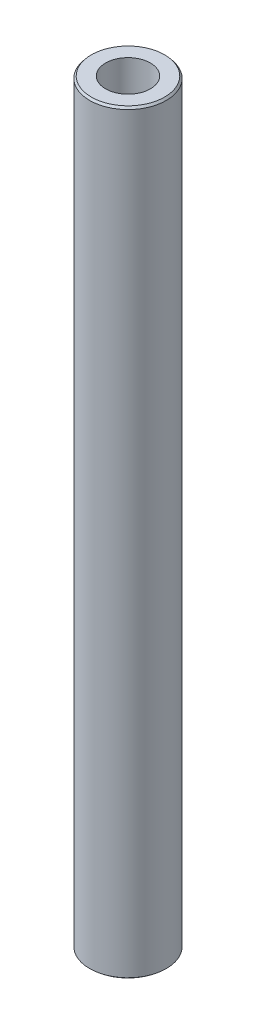
SolidWorks part; units mm, degrees
ref_plane "Front Plane" through (0, 0, 0) normal (0, 0, 1) x (1, 0, 0)
ref_plane "Top Plane" through (0, 0, 0) normal (0, 1, 0) x (1, 0, 0)
ref_plane "Right Plane" through (0, 0, 0) normal (1, 0, 0) x (0, 0, -1)
sketch "Sketch1" plane through (0, 0, 0) normal (0, 1, 0) x (1, 0, 0)
  circle A0 centre (0, 0) radius 7.5
  dimension "SHAFT_OD" = 15
extrude "Boss-Extrude1" add sketch "Sketch1" along normal blind 147.9081
sketch "Sketch2" plane through (0, 0, 0) normal (0, 1, 0) x (1, 0, 0)
  circle A0 centre (0, 0) radius 4.3902
  dimension "BORE_D" = 8.7805
extrude "Cut-Extrude1" cut sketch "Sketch2" along normal through all
chamfer "Chamfer1" distance 0.4091 angle 38.612 2 edges at (0, 147.9081, 7.5) (0, 0, 7.5) first distance on face at (0, 147.9081, 7.5) first distance on face at (0, 0, 4.3902)
